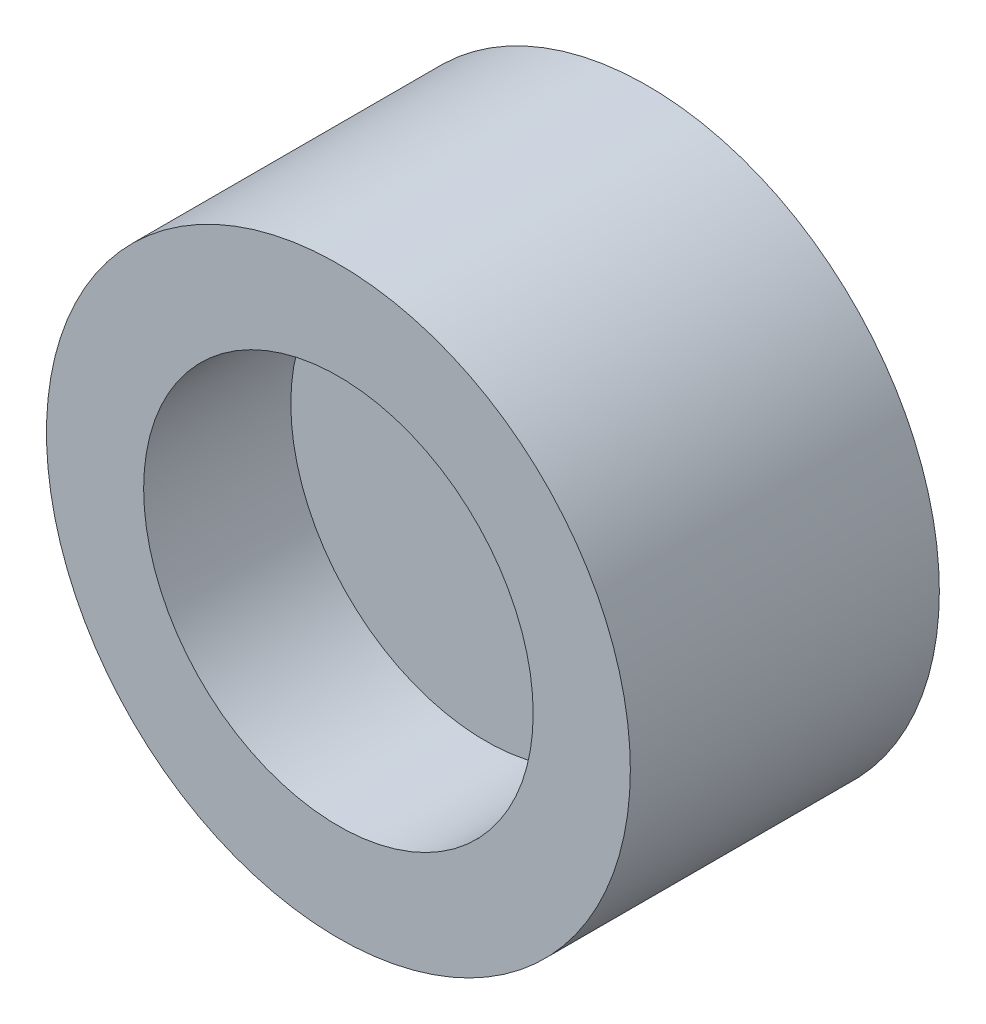
SolidWorks part; units mm, degrees
ref_plane "정면" through (0, 0, 0) normal (0, 0, 1) x (1, 0, 0)
ref_plane "윗면" through (0, 0, 0) normal (0, 1, 0) x (1, 0, 0)
ref_plane "우측면" through (0, 0, 0) normal (1, 0, 0) x (0, 0, -1)
sketch "스케치1" plane through (0, 0, 0) normal (0, 0, 1) x (1, 0, 0)
  circle A0 centre (0, 0) radius 2.5
  circle A1 centre (0, 0) radius 3.7472
  dimension "D1" = 5
extrude "보스-돌출1" add sketch "스케치1" along normal blind 2.0772 contours A0 region at (0, 0, 0)
extrude "보스-돌출2" add sketch "스케치1<3>" along normal blind 3.9662 contours A1 A0 region at (-3.6412, 0, 0)
sketch "스케치1<3>" plane through (0, 0, 0) normal (0, 0, 1) x (1, 0, 0) same geometry as "스케치1"
